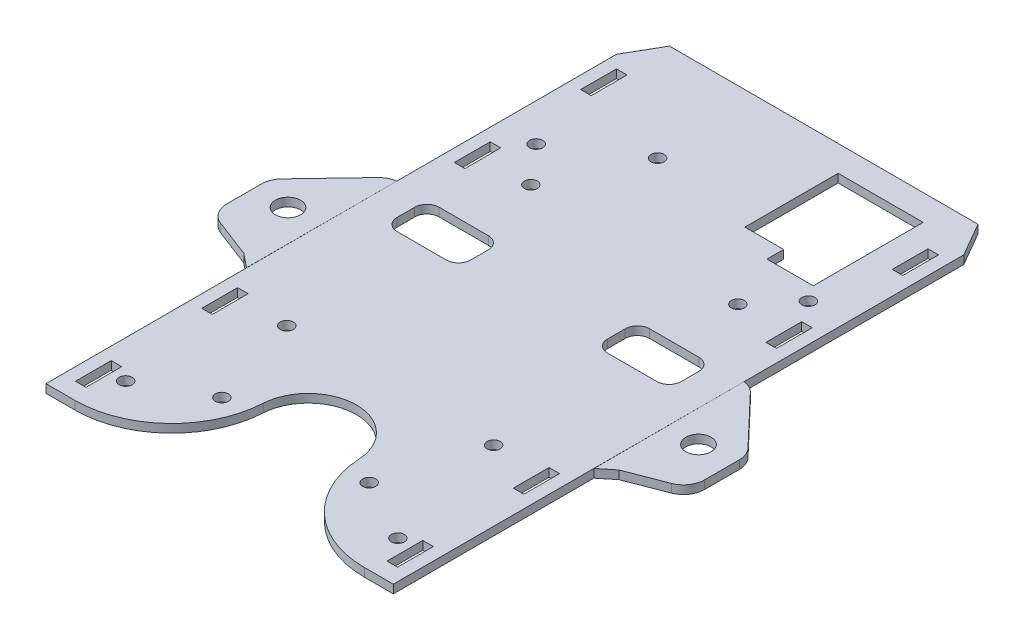
SolidWorks part; units mm, degrees
ref_plane "Front Plane" through (0, 0, 0) normal (0, 0, 1) x (1, 0, 0)
ref_plane "Top Plane" through (0, 0, 0) normal (0, 1, 0) x (1, 0, 0)
ref_plane "Right Plane" through (0, 0, 0) normal (1, 0, 0) x (0, 0, -1)
sketch "Sketch1" plane through (0, 0, 0) normal (0, 1, 0) x (1, 0, 0)
  line L0 (-1000, 0) -> (49000, 0) construction
  line L1 (0, 0) -> (0, 100.3728) construction
  line L5 (-41.25, -55) -> (-34.3696, -55)
  line L6 (41.25, -55) -> (34.3696, -55)
  line L7 (9.55, 82.35) -> (29.75, 82.35)
  line L8 (29.75, 82.35) -> (29.75, 56.25)
  line L10 (9.55, 60.2) -> (9.55, 82.35)
  line L11 (35.75, 77.5) -> (38.25, 77.5)
  line L12 (38.25, 77.5) -> (38.25, 69)
  line L13 (38.25, 69) -> (35.75, 69)
  line L14 (35.75, 69) -> (35.75, 77.5)
  line L15 (35.75, 39) -> (35.75, 47.5)
  line L16 (35.75, 47.5) -> (38.25, 47.5)
  line L17 (38.25, 47.5) -> (38.25, 39)
  line L18 (38.25, 39) -> (35.75, 39)
  line L19 (35.75, 9) -> (35.75, 17.5) construction
  line L20 (35.75, 17.5) -> (38.25, 17.5) construction
  line L21 (38.25, 17.5) -> (38.25, 9) construction
  line L22 (38.25, 9) -> (35.75, 9) construction
  line L35 (35.75, -51) -> (35.75, -42.5)
  line L36 (35.75, -42.5) -> (38.25, -42.5)
  line L37 (38.25, -42.5) -> (38.25, -51)
  line L38 (-41.25, -55) -> (-41.25, 0)
  line L39 (9.55, 60.2) -> (18.75, 60.2)
  line L40 (38.25, -51) -> (35.75, -51)
  line L42 (18.75, 56.25) -> (18.75, 60.2)
  line L43 (-38.25, -51) -> (-38.25, -42.5)
  line L44 (-38.25, -42.5) -> (-35.75, -42.5)
  line L45 (-41.25, 0) -> (-41.25, 80.5)
  line L46 (41.25, -55) -> (41.25, 0)
  line L47 (41.25, 0) -> (41.25, 80.5)
  line L48 (-41.25, 80.5) -> (-36.6408, 88.4834)
  line L49 (-36.6408, 88.4834) -> (36.6408, 88.4834)
  line L50 (41.25, 80.5) -> (36.6408, 88.4834)
  line L51 (35.75, -21) -> (35.75, -12.5)
  line L52 (35.75, -12.5) -> (38.25, -12.5)
  line L53 (38.25, -12.5) -> (38.25, -21)
  line L54 (38.25, -21) -> (35.75, -21)
  line L55 (35.75, 69) -> (35.75, 39) construction
  line L56 (-38.25, 69) -> (-38.25, 77.5)
  line L57 (-38.25, 77.5) -> (-35.75, 77.5)
  line L58 (-35.75, 77.5) -> (-35.75, 69)
  line L59 (-35.75, 69) -> (-38.25, 69)
  line L60 (-38.25, 39) -> (-38.25, 47.5)
  line L61 (-38.25, 47.5) -> (-35.75, 47.5)
  line L62 (-35.75, 47.5) -> (-35.75, 39)
  line L63 (-35.75, 39) -> (-38.25, 39)
  line L64 (-38.25, 9) -> (-38.25, 17.5) construction
  line L65 (-38.25, 17.5) -> (-35.75, 17.5) construction
  line L66 (-35.75, 17.5) -> (-35.75, 9) construction
  line L67 (-35.75, 9) -> (-38.25, 9) construction
  line L68 (-38.25, -21) -> (-38.25, -12.5)
  line L69 (-38.25, -12.5) -> (-35.75, -12.5)
  line L70 (-35.75, -12.5) -> (-35.75, -21)
  line L71 (-35.75, -21) -> (-38.25, -21)
  line L72 (18.75, 56.25) -> (29.75, 56.25)
  line L74 (-35.75, -42.5) -> (-35.75, -51)
  line L75 (-35.75, -51) -> (-38.25, -51)
  circle A2 centre (-15, 64.0223) radius 1.55
  circle A3 centre (-17.5, -36.9777) radius 1.55
  circle A6 centre (17.5, -36.9777) radius 1.55
  arc A7 (-11.4407, -33.3184) -> (-34.3696, -55) centre (-34.3696, -32.0353) cw
  arc A8 (-11.4407, -33.3184) -> (0, -22.5) centre (0, -33.9586) cw
  arc A9 (11.4407, -33.3184) -> (34.3696, -55) centre (34.3696, -32.0353) ccw
  arc A10 (11.4407, -33.3184) -> (0, -22.5) centre (0, -33.9586) ccw
  circle A11 centre (32.325, 52.5) radius 2.75 construction
  circle A12 centre (32.325, 52.5) radius 1.55
  circle A13 centre (32.325, -45) radius 1.55
  circle A14 centre (32.325, -45) radius 2.75 construction
  circle A15 centre (-32.325, 52.5) radius 1.55
  circle A16 centre (-32.325, -45) radius 1.55
  circle A17 centre (-32.325, 52.5) radius 2.75 construction
  circle A18 centre (-32.325, -45) radius 2.75 construction
  circle A19 centre (-24.575, 43.5) radius 1.55
  circle A20 centre (24.575, 43.5) radius 1.55
  circle A21 centre (24.575, -14.5) radius 1.55
  circle A22 centre (-24.575, -14.5) radius 1.55
  point P20 (-41.25, 0)
  point P23 (0, 55)
  point P26 (41.25, 0)
  point P63 (24.25, 56.25)
  point P83 (0, 88.4834)
  dimension "D20" = 5.5
  dimension "D21" = 3.1
  dimension "D22" = 64.65
  dimension "D4" = 101
  dimension "D5" = 17.5
  dimension "D6" = 15
  dimension "D7" = 64.0223
  dimension "D8" = 120
  dimension "D9" = 55
  dimension "D10" = 2
  dimension "D11" = 5
  dimension "D12" = 2.5
  dimension "D13" = 80.5
  dimension "D14" = 82.5
  dimension "D15" = 8.5
  dimension "D16" = 77.5
  dimension "D17" = 30
  dimension "D18" = 71.5
  dimension "D19" = 22.5
  dimension "D23" = 3.425
  dimension "D24" = 52.5
  dimension "D25" = 45
  dimension "D26" = 9.55
  dimension "D27" = 29.75
  dimension "D28" = 82.35
  dimension "D29" = 3.95
  dimension "D30" = 9.2
  dimension "D31" = 26.1
  dimension "D32" = 49.15
  dimension "D33" = 58
  dimension "D34" = 43.5
extrude "主结构和连接" add sketch "Sketch1" along normal blind 2 contours A10 A9 L6 L46 L47 L50 L49 L48 L45 L38 L5 A7 A8 L72 L42 L39 L10 L7 L8 L20 L21 L17 L12 L13 L14 L15 L19 region at (-0.9594, 0, -19.3711)
sketch "外部切除点示意-1" plane through (0, 0, 0) normal (0, 1, 0) x (1, 0, 0)
  line L1 (0, 0) -> (-149.6598, 0) construction
  line L2 (0, -1000) -> (0, 49000) construction
  line L3 (-41.25, 28.3195) -> (-41.2859, -7.3505)
  line L4 (41.25, 28.3195) -> (41.2859, -7.3505)
  line L5 (4.0667, 88.4834) -> (4.0667, 66.8745)
  line L7 (4.0667, 66.8745) -> (-29.1468, 66.8745)
  line L8 (-29.1468, 66.8745) -> (-29.1468, 88.4834)
  line L10 (-29.1468, 88.4834) -> (4.0667, 88.4834)
  arc A0 (-41.25, 28.3195) -> (-41.2859, -7.3505) centre (-78.8424, 10.5223) cw
  arc A3 (41.25, 28.3195) -> (41.2859, -7.3505) centre (78.8424, 10.5223) ccw
sketch "底部天线接口" plane through (0, 0, 0) normal (0, 1, 0) x (1, 0, 0)
  line L1 (-37.25, 10.4804) -> (37.25, 10.4804) construction
  line L3 (0, 10.4804) -> (0, 122.9252) construction
  line L4 (0, -201000) -> (0, 249000) construction
  line L21 (-33.75, 22.9804) -> (0, 22.9804) construction
  line L22 (-30.85, 27.9804) -> (-19.15, 27.9804)
  line L23 (-25, 27.9804) -> (-25, 15.707) construction
  line L24 (-30.85, 17.9804) -> (-19.15, 17.9804)
  line L25 (-33.75, 25.0804) -> (-33.75, 20.8804)
  line L26 (-16.25, 25.0804) -> (-16.25, 20.8804)
  line L27 (0, 0) -> (0, 100.3728) construction
  line L30 (33.75, 25.0804) -> (33.75, 20.8804)
  line L31 (30.85, 17.9804) -> (19.15, 17.9804)
  line L32 (16.25, 25.0804) -> (16.25, 20.8804)
  line L33 (30.85, 27.9804) -> (19.15, 27.9804)
  line L36 (-201000, 0) -> (249000, 0) construction
  line L47 (-44.5511, -4.7023) -> (-41.2859, -7.3505)
  line L48 (-41.2859, -7.3505) -> (-41.25, 28.3195)
  line L54 (-56.75, 13.6707) -> (-56.75, 0)
  line L55 (-56.75, 0) -> (-44.5511, -4.7023)
  line L62 (-41.25, 28.3195) -> (-42.8045, 28.3195)
  line L63 (-42.8045, 28.3195) -> (-56.75, 13.6707)
  line L64 (42.8045, 28.3195) -> (56.75, 13.6707)
  line L65 (41.25, 28.3195) -> (42.8045, 28.3195)
  line L66 (41.2859, -7.3505) -> (41.25, 28.3195)
  line L67 (44.5511, -4.7023) -> (41.2859, -7.3505)
  line L68 (56.75, 0) -> (44.5511, -4.7023)
  line L69 (56.75, 13.6707) -> (56.75, 0)
  circle A5 centre (-48.75, 9.9804) radius 3
  arc A12 (-41.2859, -7.3505) -> (-41.25, 28.3195) centre (-78.8424, 10.5223) ccw construction
  arc A13 (41.25, 28.3195) -> (41.2859, -7.3505) centre (78.8424, 10.5223) ccw construction
  arc A18 (-30.85, 27.9804) -> (-33.75, 25.0804) centre (-30.85, 25.0804) ccw
  arc A19 (-19.15, 27.9804) -> (-16.25, 25.0804) centre (-19.15, 25.0804) cw
  arc A20 (-30.85, 17.9804) -> (-33.75, 20.8804) centre (-30.85, 20.8804) cw
  arc A21 (-19.15, 17.9804) -> (-16.25, 20.8804) centre (-19.15, 20.8804) ccw
  circle A25 centre (48.75, 9.9804) radius 3
  arc A26 (30.85, 27.9804) -> (33.75, 25.0804) centre (30.85, 25.0804) cw
  arc A27 (30.85, 17.9804) -> (33.75, 20.8804) centre (30.85, 20.8804) ccw
  arc A28 (19.15, 17.9804) -> (16.25, 20.8804) centre (19.15, 20.8804) cw
  arc A29 (19.15, 27.9804) -> (16.25, 25.0804) centre (19.15, 25.0804) ccw
  dimension "D1" = 6
  dimension "D2" = 17.5
  dimension "D4" = 2.9
  dimension "D3" = 10
  dimension "D5" = 25
  dimension "D6" = 12.5
  dimension "D7" = 11.5
  dimension "D8" = 0.5
  dimension "D9" = 8
extrude "天线接口-1" add sketch "底部天线接口" along normal up to surface (2 mm away) from surface contours A5 | A25 region at (-50.5107, 0, 1.9883) region at (49.4956, 0, -20.7269) up to face at (24.575, 2, 16.05) starting at face at (24.575, 0, 16.05)
extrude "天线走线槽" cut sketch "底部天线接口<3>" along normal through all both and the other way through all contours L24 A21 L26 A19 L22 A18 L25 A20 | L33 A29 L32 A28 L31 A27 L30 A26 region at (-25, 0, -22.9804) region at (25, 0, -22.9804)
sketch "底部天线接口<3>" plane through (0, 0, 0) normal (0, 1, 0) x (1, 0, 0) same geometry as "底部天线接口"
fillet "圆角1" radius 5 3 edges at (-56.75, 1, 0) (-56.75, 1, -13.6707) (-42.8045, 1, -28.3195)
fillet "圆角2" radius 5 3 edges at (56.75, 1, 0) (56.75, 1, -13.6707) (42.8045, 1, -28.3195)
